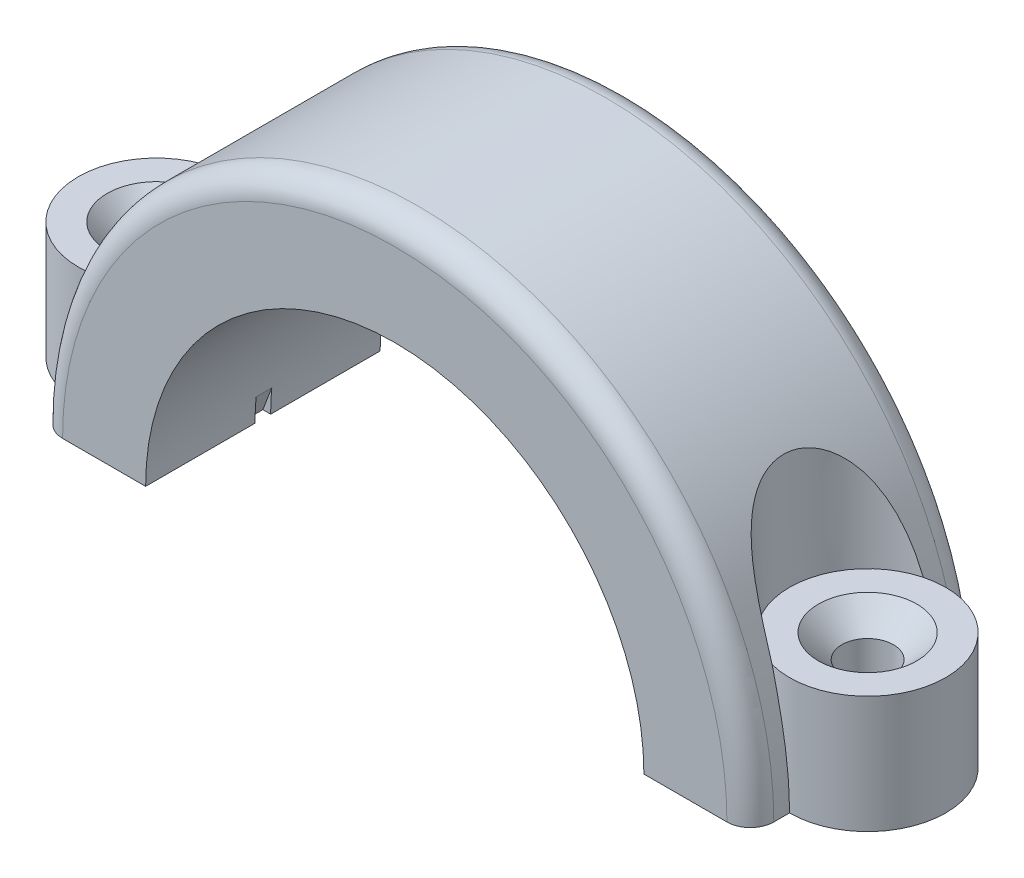
SolidWorks part; units mm, degrees
material "Low alloy steel, AISI 4340, normalized"
ref_plane "Front Plane" through (0, 0, 0) normal (0, 0, 1) x (1, 0, 0)
ref_plane "Top Plane" through (0, 0, 0) normal (0, 1, 0) x (1, 0, 0)
ref_plane "Right Plane" through (0, 0, 0) normal (1, 0, 0) x (0, 0, -1)
sketch "Sketch1" plane through (0, 0, 0) normal (0, 0, 1) x (1, 0, 0)
  line L0 (-45.5, 0) -> (-31.875, 0)
  line L1 (31.875, 0) -> (45.5, 0)
  arc A0 (-45.5, 0) -> (45.5, 0) centre (0, 0) cw
  arc A1 (-31.875, 0) -> (31.875, 0) centre (0, 0) cw
  dimension "D1" = 31.875
  dimension "D2" = 45.5
extrude "Boss-Extrude1" add sketch "Sketch1" along normal mid plane 30
sketch "Sketch2" plane through (0, 0, 0) normal (0, -1, 0) x (1, 0, 0)
  line L0 (-45.5, 15) -> (-45.5, -15) construction
  circle A0 centre (-45.5, 0) radius 10
  dimension "D1" = 20
extrude "Boss-Extrude2" add sketch "Sketch2" against normal blind 15
extrude "Cut-Extrude1" cut sketch "Sketch2<2>" against normal blind 45 draft 3 from offset 15 draft outward yes offset against normal yes
sketch "Sketch2<2>" plane through (0, 0, 0) normal (0, -1, 0) x (1, 0, 0) same geometry as "Sketch2"
hole_wizard "CSK for M6 Flat Head Machine Screw1" positions "Sketch3" profile "Sketch4" countersink size "M6" standard "ANSI Metric" end condition through all
sketch "Sketch3" plane through (0, 15, 0) normal (0, 1, 0) x (1, 0, 0)
  point P0 (-45.5, 0)
sketch "Sketch4" plane through (-45.5, 15, 0) normal (1, 0, 0) x (0, 0, 1)
  line L0 (0, 0) -> (0, 15)
  line L1 (0, 15) -> (3.3, 15)
  line L2 (3.3, 15) -> (3.3, 3)
  line L3 (3.3, 3) -> (6.3, 0)
  line L5 (6.3, 0) -> (0, 0)
  line L6 (-3.3, 3) -> (-6.3, 0) construction
  line L11 (0, -6.35) -> (0, 107.95) construction
  dimension "Thru Hole Dia." = 6.6
  dimension "Thru Hole Depth" = 15
  dimension "Near C'Sink Dia." = 12.6
  dimension "Near C'Sink Angle" = 90
mirror "Mirror1" about plane through (0, 0, 0) normal (1, 0, 0) of "Boss-Extrude2", "CSK for M6 Flat Head Machine Screw1", "Cut-Extrude1"
fillet "Fillet1" radius 3 2 edges at (0, 45.5, 15) (0, 45.5, -15)
sketch "Sketch5" plane through (0, 0, 10) normal (0, 1, 0) x (1, 0, 0)
  line L0 (-31.875, -5) -> (-31.875, 25) construction
  line L1 (-32.875, 9) -> (-31.875, 9)
  line L2 (-32.875, 9) -> (-32.875, 11)
  line L3 (-32.875, 11) -> (-31.875, 11)
  line L4 (-31.875, 9) -> (-31.875, 11)
  point P9 (-31.875, 10)
  dimension "D1" = 2
  dimension "D2" = 1
sketch "Sketch6" plane through (0, 0, 0) normal (0, 0, 1) x (1, 0, 0)
  line L0 (-32.875, 0) -> (-31.7335, 3)
  line L1 (-42.5, 0) -> (-31.875, 0) construction
  arc A0 (31.875, 0) -> (-31.875, 0) centre (0, 0) ccw construction
  dimension "D1" = 3
  dimension "D2" = 1
sweep "Cut-Sweep1" cut profiles "Sketch5" path "Sketch6"
equation "\"D1@Sketch1\"=63.75/2"
equation "\"D2@Sketch5\"=1mm"
equation "\"D1@Sketch5\"=2mm"
